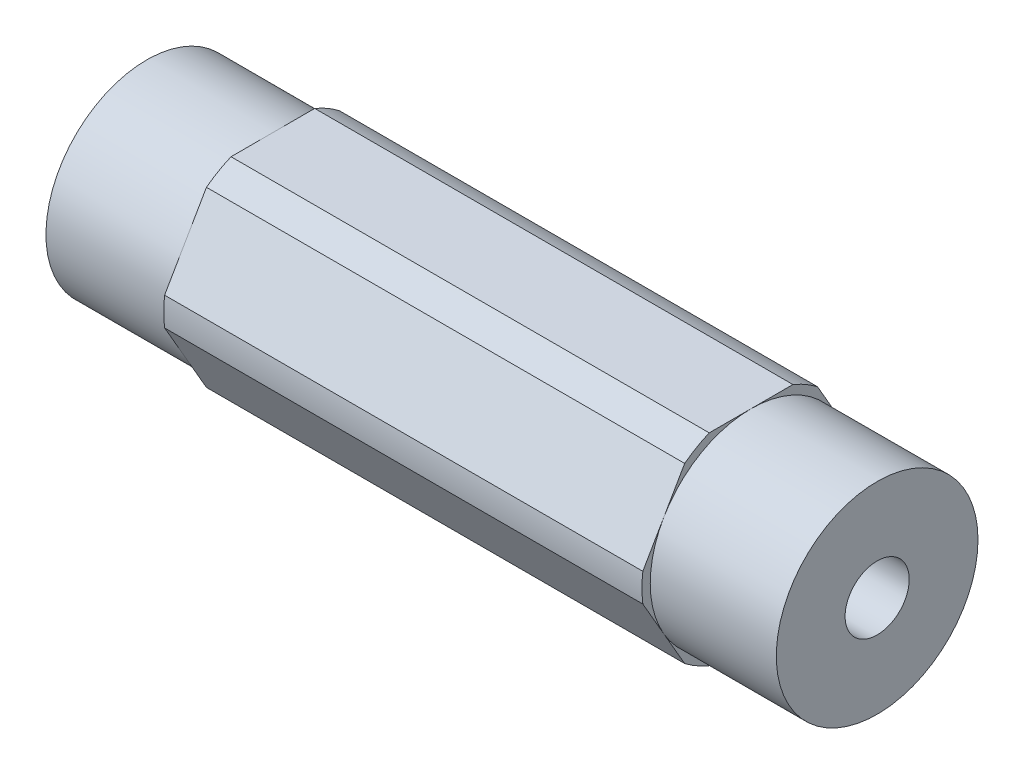
SolidWorks part; units mm, degrees
material "7075-T6 (SN)"
ref_plane "Front Plane" through (0, 0, 0) normal (0, 0, 1) x (1, 0, 0)
ref_plane "Top Plane" through (0, 0, 0) normal (0, 1, 0) x (1, 0, 0)
ref_plane "Right Plane" through (0, 0, 0) normal (1, 0, 0) x (0, 0, -1)
sketch "Sketch1" plane through (0, 0, 0) normal (1, 0, 0) x (0, 0, -1)
  line L1 (3.6662, 6.35) -> (-3.6662, 6.35)
  line L2 (-3.6662, 6.35) -> (-7.3323, 0)
  line L3 (-7.3323, 0) -> (-3.6662, -6.35)
  line L4 (-3.6662, -6.35) -> (3.6662, -6.35)
  line L5 (3.6662, -6.35) -> (7.3323, 0)
  line L6 (7.3323, 0) -> (3.6662, 6.35)
  circle A0 centre (0, 0) radius 6.875
  circle A1 centre (0, 0) radius 2.0193
  circle A2 centre (0, 0) radius 6.35 construction
  dimension "D1" = 12.7
  dimension "D2" = 13.75
  dimension "D3" = 4.0386
extrude "Boss-Extrude1" add sketch "Sketch1" along normal mid plane 45.9867 contours L6 A0 L1 L2 L3 L4 L5 A1 region at (0, 5.7918, -3.3439)
sketch "Sketch3" plane through (22.9933, 0, 0) normal (1, 0, 0) x (0, 0, -1)
  circle A0 centre (0, 0) radius 6.35
  dimension "D1" = 12.7
extrude "Cut-Extrude-Thin1" cut sketch "Sketch3" against normal blind 7.9375 thin thin type one direction wall 2.54
mirror "Mirror1" about plane through (0, 0, 0) normal (1, 0, 0) of "Cut-Extrude-Thin1"
equation "\"D2@Sketch1\"=13.75mm"
